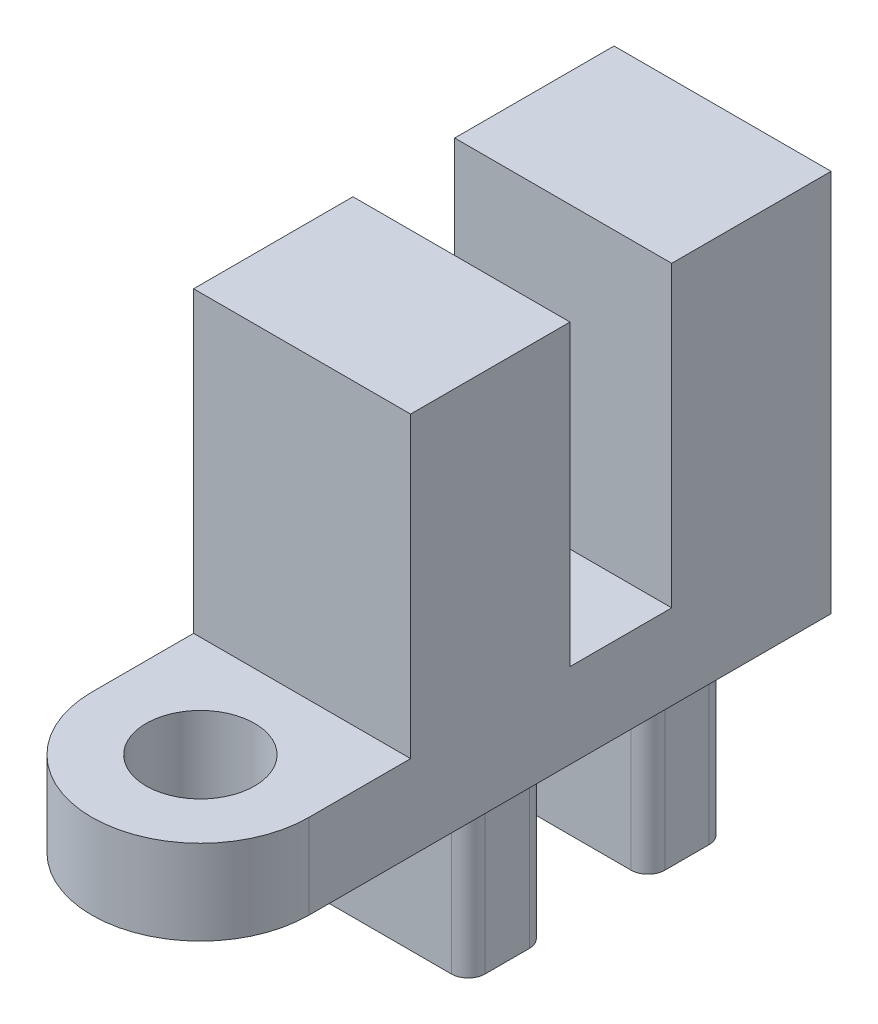
SolidWorks part; units mm, degrees
material "ABS"
ref_plane "Plan de face" through (0, 0, 0) normal (0, 0, 1) x (1, 0, 0)
ref_plane "Plan de dessus" through (0, 0, 0) normal (0, 1, 0) x (1, 0, 0)
ref_plane "Plan de droite" through (0, 0, 0) normal (1, 0, 0) x (0, 0, -1)
sketch "Esquisse1" plane through (0, 0, 0) normal (0, 1, 0) x (1, 0, 0)
  line L0 (-3.2, 6.2) -> (3.2, 6.2)
  line L1 (3.2, 6.2) -> (3.2, -9.2)
  line L2 (-3.2, -9.2) -> (-3.2, 6.2)
  line L3 (0, 14.5896) -> (0, -23.3572) construction
  arc A0 (3.2, -9.2) -> (-3.2, -9.2) centre (0, -9.2) cw
  circle A1 centre (0, -9.2) radius 1.6
  dimension "D1" = 6.4
  dimension "D4" = 3.2
  dimension "D2" = 6.2
  dimension "D3" = 18.6
extrude "Extrusion1" add sketch "Esquisse1" against normal blind 2.5
sketch "Esquisse2" plane through (0, 0, 0) normal (0, 1, 0) x (-1, 0, 0)
  line L0 (-3.2, 9.2) -> (-3.2, -6.2) construction
  line L1 (3.2, -6.2) -> (-3.2, -6.2)
  line L2 (3.2, -6.2) -> (3.2, -1.5)
  line L3 (3.2, -1.5) -> (-3.2, -1.5)
  line L4 (-3.2, -6.2) -> (-3.2, -1.5)
  line L5 (3.2, -6.2) -> (3.2, 9.2) construction
  line L6 (3.2, 1.5) -> (-3.2, 1.5)
  line L7 (3.2, 1.5) -> (3.2, 6.2)
  line L8 (3.2, 6.2) -> (-3.2, 6.2)
  line L9 (-3.2, 1.5) -> (-3.2, 6.2)
  line L10 (5.1781, 0) -> (-7.6076, 0) construction
  dimension "D1" = 3
  dimension "D2" = 12.4
extrude "Extrusion2" add sketch "Esquisse2" along normal blind 8.8
sketch "Esquisse3" plane through (0, -2.5, 0) normal (0, -1, 0) x (1, 0, 0)
  line L0 (0, 6.698) -> (0, -7.8901) construction
  line L1 (-2, 3.8) -> (2, 3.8)
  line L2 (-2.5, 3.3) -> (-2.5, 2)
  line L3 (-2, 1.5) -> (2, 1.5)
  line L4 (2.5, 3.3) -> (2.5, 2)
  line L5 (-2, -1.5) -> (2, -1.5)
  line L6 (-2.5, -2) -> (-2.5, -3.3)
  line L7 (-2, -3.8) -> (2, -3.8)
  line L8 (2.5, -2) -> (2.5, -3.3)
  line L10 (12.3571, 0) -> (-12.3571, 0) construction
  arc A0 (-2, 3.8) -> (-2.5, 3.3) centre (-2, 3.3) ccw
  arc A1 (2, 3.8) -> (2.5, 3.3) centre (2, 3.3) cw
  arc A2 (2, 1.5) -> (2.5, 2) centre (2, 2) ccw
  arc A3 (-2.5, 2) -> (-2, 1.5) centre (-2, 2) ccw
  arc A4 (-2, -1.5) -> (-2.5, -2) centre (-2, -2) ccw
  arc A5 (2, -1.5) -> (2.5, -2) centre (2, -2) cw
  arc A6 (2, -3.8) -> (2.5, -3.3) centre (2, -3.3) ccw
  arc A7 (-2.5, -3.3) -> (-2, -3.8) centre (-2, -3.3) ccw
  point P24 (2.5, -1.5)
  point P27 (2.5, -3.8)
  point P30 (-2.5, -3.8)
  dimension "D4" = 0.5
  dimension "D1" = 5
  dimension "D2" = 2.3
  dimension "D3" = 3
extrude "Extrusion3" add sketch "Esquisse3" along normal blind 4.8
sketch "Esquisse4" plane through (0, 0, 0) normal (1, 0, 0) x (0, 0, -1)
  line L0 (6.2, 6.07) -> (-6.2, 6.07) construction
  line L1 (6.2, -2.5) -> (6.2, 8.8) construction
  line L2 (-6.2, 8.8) -> (-6.2, 0) construction
  line L3 (6.2, 8.8) -> (1.5, 8.8) construction
  dimension "D1" = 2.73
ref_axis "Axe1" through (0, 6.07, 6.2) along (0, 0, -1)
